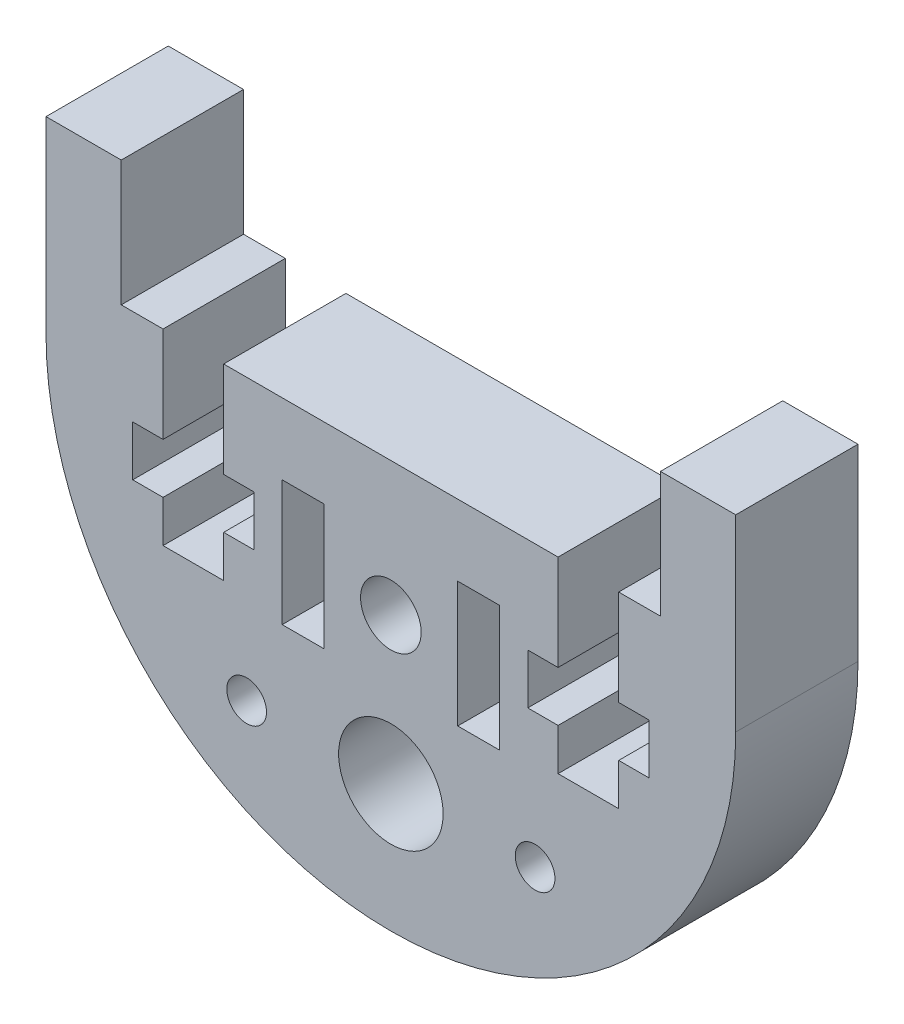
SolidWorks part; units mm, degrees
material "Acrylic (Medium-high impact)"
ref_plane "Front Plane" through (0, 0, 0) normal (0, 0, 1) x (1, 0, 0)
ref_plane "Top Plane" through (0, 0, 0) normal (0, 1, 0) x (1, 0, 0)
ref_plane "Right Plane" through (0, 0, 0) normal (1, 0, 0) x (0, 0, -1)
sketch "Model" plane through (0, 0, 0) normal (0, 0, 1) x (1, 0, 0)
  line L0 (545.5095, 560.9325) -> (553.5095, 560.9325)
  line L1 (553.5095, 547.5325) -> (553.5095, 543.2575) construction
  line L2 (553.5095, 547.5325) -> (553.5095, 543.2575) construction
  line L3 (546.6095, 547.5325) -> (553.5095, 547.5325) construction
  line L4 (560.4095, 547.5325) -> (553.5095, 547.5325) construction
  line L5 (553.5095, -441.0675) -> (553.5095, 49558.9325) construction
  line L6 (553.5095, 547.5325) -> (553.5095, 543.2575) construction
  line L7 (553.5095, 543.2575) -> (553.5095, 547.5325) construction
  line L8 (561.5095, 556.3566) -> (561.5095, 560.9325)
  line L9 (560.0595, 556.3566) -> (561.5095, 556.3566)
  line L10 (560.0595, 553.9565) -> (560.0595, 556.3566)
  line L11 (561.5095, 553.9565) -> (560.0595, 553.9565)
  line L12 (561.5095, 551.9565) -> (561.5095, 553.9565)
  line L13 (564.4095, 551.9565) -> (561.5095, 551.9565)
  line L14 (564.4095, 553.9565) -> (564.4095, 551.9565)
  line L15 (565.8595, 553.9565) -> (564.4095, 553.9565)
  line L16 (565.8595, 556.3566) -> (565.8595, 553.9565)
  line L17 (564.4095, 556.3566) -> (565.8595, 556.3566)
  line L18 (564.4095, 560.9325) -> (564.4095, 556.3566)
  line L19 (566.4095, 560.9325) -> (564.4095, 560.9325)
  line L20 (566.4095, 566.9325) -> (566.4095, 560.9325)
  line L21 (570.0095, 566.9325) -> (566.4095, 566.9325)
  line L22 (570.0095, 557.9325) -> (570.0095, 566.9325)
  line L23 (561.5095, 560.9325) -> (553.5095, 560.9325)
  line L24 (553.5095, 547.5325) -> (553.5095, 555.4893) construction
  line L25 (542.6095, 560.9325) -> (545.5095, 560.9325) construction
  line L26 (544.0595, 560.9325) -> (544.0595, 551.9565) construction
  line L27 (562.9595, 560.9325) -> (562.9595, 551.9565) construction
  line L28 (561.5095, 560.9325) -> (564.4095, 560.9325) construction
  line L29 (558.7095, 551.5325) -> (556.7095, 551.5325)
  line L30 (548.3095, 551.5325) -> (550.3095, 551.5325)
  line L31 (548.3095, 551.5325) -> (548.3095, 557.5325)
  line L32 (548.3095, 557.5325) -> (550.3095, 557.5325)
  line L33 (550.3095, 551.5325) -> (550.3095, 557.5325)
  line L34 (558.7095, 551.5325) -> (558.7095, 557.5325)
  line L35 (558.7095, 557.5325) -> (556.7095, 557.5325)
  line L36 (556.7095, 551.5325) -> (556.7095, 557.5325)
  line L41 (537.0095, 557.9325) -> (537.0095, 566.9325)
  line L42 (537.0095, 566.9325) -> (540.6095, 566.9325)
  line L43 (540.6095, 566.9325) -> (540.6095, 560.9325)
  line L44 (540.6095, 560.9325) -> (542.6095, 560.9325)
  line L45 (542.6095, 560.9325) -> (542.6095, 556.3566)
  line L46 (542.6095, 556.3566) -> (541.1595, 556.3566)
  line L47 (541.1595, 556.3566) -> (541.1595, 553.9565)
  line L48 (541.1595, 553.9565) -> (542.6095, 553.9565)
  line L49 (542.6095, 553.9565) -> (542.6095, 551.9565)
  line L50 (542.6095, 551.9565) -> (545.5095, 551.9565)
  line L51 (545.5095, 551.9565) -> (545.5095, 553.9565)
  line L52 (545.5095, 553.9565) -> (546.9595, 553.9565)
  line L53 (546.9595, 553.9565) -> (546.9595, 556.3566)
  line L54 (546.9595, 556.3566) -> (545.5095, 556.3566)
  line L55 (545.5095, 556.3566) -> (545.5095, 560.9325)
  circle A0 centre (546.6095, 547.5325) radius 0.95
  circle A1 centre (553.5095, 547.5325) radius 2.5
  circle A2 centre (553.5095, 554.5325) radius 1.45
  arc A4 (570.0095, 557.9325) -> (537.0095, 557.9325) centre (553.5095, 557.9325) cw
  circle A8 centre (560.4095, 547.5325) radius 0.95
  point P7 (544.0595, 560.9325)
  point P18 (553.5095, 554.5325)
  point P41 (550.3095, 554.5325)
  point P42 (552.0595, 554.5325)
  point P47 (556.7095, 554.5325)
  point P48 (553.5095, 550.0325)
  dimension "D10" = 6.9
  dimension "D9" = 1.9
  dimension "D14" = 5
  dimension "D16" = 2.9
  dimension "D1" = 3.6
  dimension "D2" = 6
  dimension "D3" = 9
  dimension "D4" = 2.4001
  dimension "D5" = 1.45
  dimension "D6" = 4.5759
  dimension "D7" = 2
  dimension "D8" = 2
  dimension "D11" = 8
  dimension "D12" = 4
  dimension "D13" = 2.9
  dimension "D15" = 3.4
  dimension "D17" = 2
  dimension "D18" = 6
  dimension "D19" = 1.75
  dimension "D20" = 1.35
extrude "Boss-Extrude2" add sketch "Model" along normal blind 5.85 contours A4 L22 L21 L20 L19 L18 L17 L16 L15 L14 L13 L12 L11 L10 L9 L8 L23 L0 L55 L54 L53 L52 L51 L50 L49 L48 L47 L46 L45 L44 L43 L42 L41 A1 A0 A8 region at (549.5095, 560.5154, 0)
